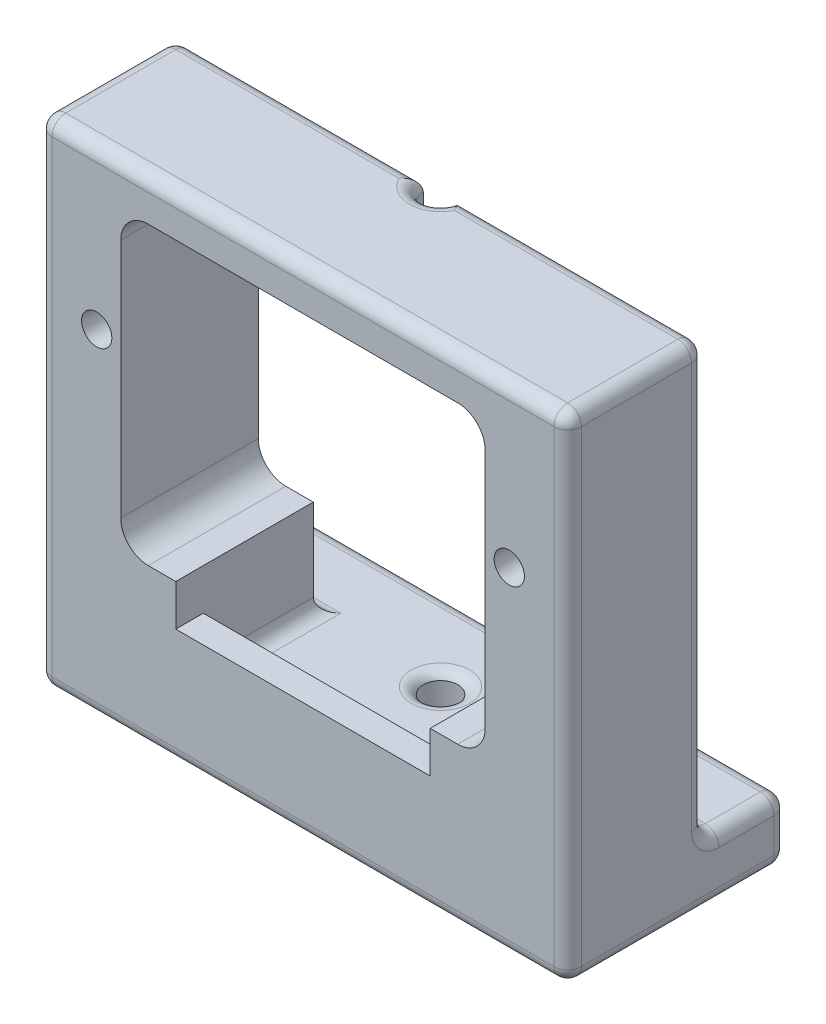
SolidWorks part; units mm, degrees
ref_plane "Front" through (0, 0, 0) normal (0, 0, 1) x (1, 0, 0)
ref_plane "Top" through (0, 0, 0) normal (0, 1, 0) x (1, 0, 0)
ref_plane "Right" through (0, 0, 0) normal (1, 0, 0) x (0, 0, -1)
sketch "Sketch1" plane through (0, 0, 0) normal (0, 0, 1) x (1, 0, 0)
  line L0 (-9.25, -12.25) -> (9.25, -12.25) construction
  line L1 (-11.25, 10.75) -> (11.25, 10.75)
  line L2 (-13.25, 8.75) -> (-13.25, -8.75)
  line L3 (-11.25, -10.75) -> (11.25, -10.75)
  line L4 (13.25, 8.75) -> (13.25, -8.75)
  line L5 (-19.25, 13.75) -> (19.25, 13.75)
  line L6 (-19.25, 13.75) -> (-19.25, -13.75)
  line L7 (-19.25, -13.75) -> (19.25, -13.75)
  line L8 (19.25, 13.75) -> (19.25, -13.75)
  line L9 (-9.25, -10.75) -> (9.25, -10.75)
  line L10 (-9.25, -10.75) -> (-9.25, -13.75)
  line L11 (-9.25, -13.75) -> (9.25, -13.75)
  line L12 (9.25, -10.75) -> (9.25, -13.75)
  line L13 (-15, 2.25) -> (15, 2.25) construction
  arc A0 (11.25, 10.75) -> (13.25, 8.75) centre (11.25, 8.75) cw
  arc A1 (13.25, -8.75) -> (11.25, -10.75) centre (11.25, -8.75) cw
  arc A2 (-11.25, -10.75) -> (-13.25, -8.75) centre (-11.25, -8.75) cw
  arc A3 (-13.25, 8.75) -> (-11.25, 10.75) centre (-11.25, 8.75) cw
  circle A4 centre (-15, 2.25) radius 1.1
  circle A5 centre (15, 2.25) radius 1.1
  point P4 (0, 10.75)
  point P6 (13.25, 0)
  point P17 (0, -12.25)
  point P30 (0, 2.25)
  dimension "D8" = 2
  dimension "D9" = 30
  dimension "D10" = 2.2
  dimension "D1" = 26.5
  dimension "D2" = 21.5
  dimension "D3" = 3
  dimension "D4" = 6
  dimension "D5" = 6
  dimension "D6" = 3
  dimension "D7" = 18.5
  dimension "D11" = 8.5
extrude "Boss-Extrude1" add sketch "Sketch1" along normal blind 10 contours L2 A3 L1 A0 L4 A1 L3 L12 L7 L8 L5 L6 L10 A2 region at (-12.9988, 10.4988, 0)
sketch "Sketch2" plane through (0, -13.75, 0) normal (0, -1, 0) x (1, 0, 0)
  line L0 (19.25, 10) -> (19.25, 0) construction
  line L1 (-19.25, 10) -> (19.25, 10)
  line L2 (-19.25, 10) -> (-19.25, 8)
  line L3 (-19.25, 8) -> (19.25, 8)
  line L4 (19.25, 10) -> (19.25, 8)
  line L6 (-19.25, 8) -> (-9.25, 8)
  line L7 (-19.25, 8) -> (-19.25, 0)
  line L8 (-19.25, 0) -> (-9.25, 0)
  line L9 (-9.25, 8) -> (-9.25, 0)
  line L10 (19.25, 8) -> (9.25, 8)
  line L11 (19.25, 8) -> (19.25, 0)
  line L12 (19.25, 0) -> (9.25, 0)
  line L13 (9.25, 8) -> (9.25, 0)
  line M3 (9.25, 0) -> (19.25, 0)
  line M4 (19.25, 0) -> (19.25, 10)
  line M5 (19.25, 10) -> (9.25, 10)
  line M6 (9.25, 10) -> (9.25, 0)
  dimension "D1" = 2
extrude "Boss-Extrude2" add sketch "Sketch2" along normal blind 4 contours L9 L3 L7 L8 | L2 L3 L1 M6 | L3 M6 M4 M5 | L3 M6 M3 M4 region at (-5, -13.75, 9) region at (14.25, -13.75, 9) region at (-14.25, -13.75, 4) region at (14.25, -13.75, 4)
sketch "Sketch3" plane through (0, -17.75, 0) normal (0, -1, 0) x (1, 0, 0)
  line L1 (-19.25, 10) -> (19.25, 10)
  line L2 (-19.25, 10) -> (-19.25, 0)
  line L3 (-19.25, 0) -> (19.25, 0)
  line L4 (19.25, 10) -> (19.25, 0)
extrude "Boss-Extrude3" add sketch "Sketch3" along normal blind 4.5
sketch "Sketch4" plane through (0, -22.25, 0) normal (0, -1, 0) x (1, 0, 0)
  line L0 (19.25, 0) -> (19.25, 10) construction
  line L1 (-19.25, 0) -> (19.25, 0)
  line L2 (-19.25, 0) -> (-19.25, -6)
  line L3 (-19.25, -6) -> (19.25, -6)
  line L4 (19.25, 0) -> (19.25, -6)
  dimension "D1" = 6
extrude "Boss-Extrude4" add sketch "Sketch4" against normal up to surface (4.5 mm away) up to face at (0, -17.75, 4)
sketch "Sketch5" plane through (0, -22.25, 0) normal (0, -1, 0) x (1, 0, 0)
  circle A0 centre (0, 0) radius 2.375
  point P2 (0, 0)
  dimension "D1" = 4.75
extrude "Cut-Extrude1" cut sketch "Sketch5" against normal blind 4
sketch "Sketch6" plane through (0, -18.25, 0) normal (0, -1, 0) x (1, 0, 0)
  circle A0 centre (0, 0) radius 1.25
  dimension "D1" = 2.5
extrude "Cut-Extrude2" cut sketch "Sketch6" against normal through all
fillet "Fillet1" radius 1 24 edges at (-14.25, -17.75, 0) (14.25, -17.75, 0) (9.25, -17.75, 4) (0, -17.75, 8) (-9.25, -17.75, 4) (0, -17.75, -1.25) (-19.25, -4.25, 10) (-19.25, -22.25, 2) (-19.25, -17.75, -3) (-19.25, -2, 0) (-19.25, -20, -6) (0, -22.25, -6) (0, -17.75, -6) (10.25, 13.75, 0) (0, 13.75, 10) (-19.25, 13.75, 5) (-10.25, 13.75, 0) (0, 13.75, 1.25) (19.25, -17.75, -3) (19.25, -20, -6) (19.25, -22.25, 2) (19.25, -4.25, 10) (19.25, 13.75, 5) (19.25, -2, 0)
fillet "Fillet2" radius 1 3 edges at (18.9571, -21.9571, 9.7071) (-18.9571, -21.9571, 9.7071) (0, -22.25, 10)
